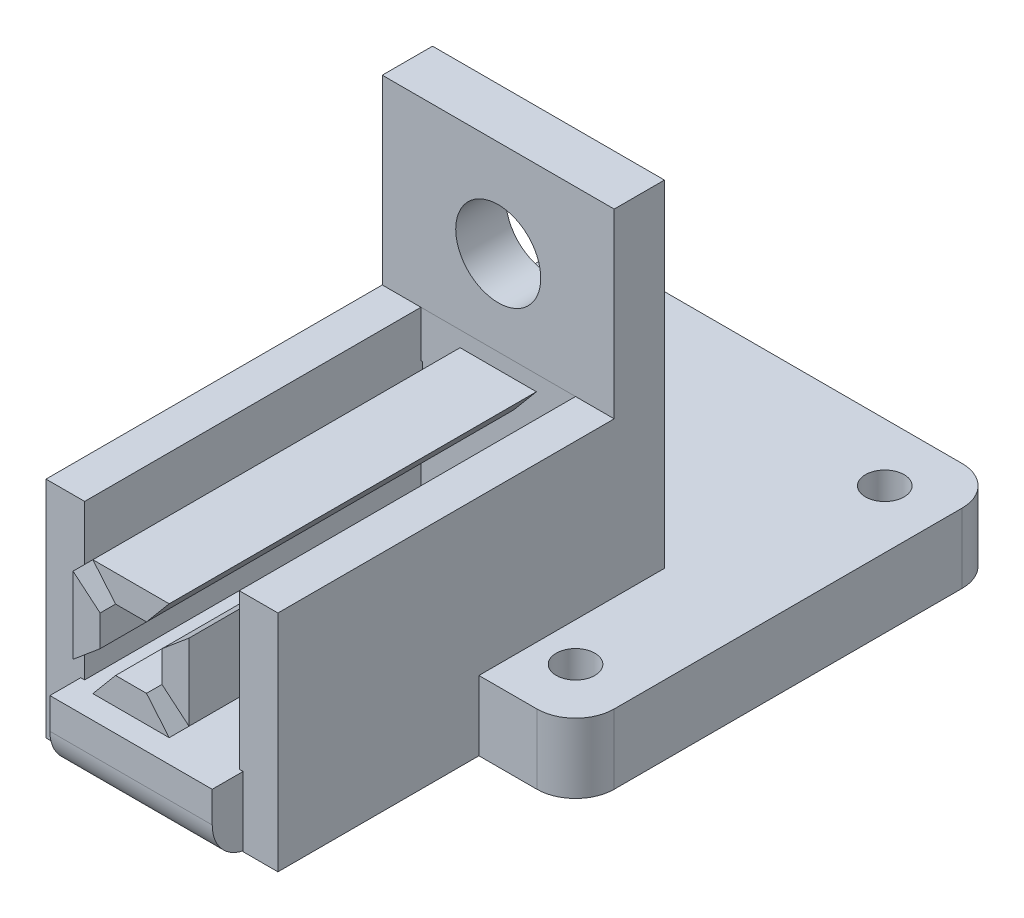
SolidWorks part; units mm, degrees
ref_plane "Front Plane" through (0, 0, 0) normal (0, 0, 1) x (1, 0, 0)
ref_plane "Top Plane" through (0, 0, 0) normal (0, 1, 0) x (1, 0, 0)
ref_plane "Right Plane" through (0, 0, 0) normal (1, 0, 0) x (0, 0, -1)
sketch "Sketch1" plane through (0, 0, 0) normal (0, 1, 0) x (1, 0, 0)
  line L0 (27.5, 55) -> (27.5, 0) construction
  line L1 (5, 0) -> (50, 0)
  line L2 (0, 5) -> (0, 50)
  line L3 (5, 55) -> (50, 55)
  line L4 (55, 5) -> (55, 50)
  line L5 (0, 55) -> (7.5, 55) construction
  line L6 (0, 55) -> (0, 47.5) construction
  line L7 (0, 47.5) -> (7.5, 47.5) construction
  line L8 (7.5, 55) -> (7.5, 47.5) construction
  line L9 (0, 27.5) -> (55, 27.5) construction
  circle A0 centre (7.5, 47.5) radius 2.5
  circle A1 centre (47.5, 47.5) radius 2.5
  circle A2 centre (47.5, 7.5) radius 2.5
  circle A3 centre (7.5, 7.5) radius 2.5
  arc A4 (50, 0) -> (55, 5) centre (50, 5) ccw
  arc A5 (50, 55) -> (55, 50) centre (50, 50) cw
  arc A6 (0, 50) -> (5, 55) centre (5, 50) cw
  arc A7 (5, 0) -> (0, 5) centre (5, 5) cw
  point P23 (55, 55)
  point P29 (0, 0)
  dimension "D3" = 2
  dimension "D5" = 5
  dimension "D1" = 55
  dimension "D2" = 55
  dimension "D4" = 2
extrude "Boss-Extrude2" add sketch "Sketch1" along normal blind 8 and the other way blind 1
sketch "Sketch2" plane through (0, 8, 0) normal (0, 1, 0) x (1, 0, 0)
  line L0 (0, 27.5) -> (55, 27.5)
  line L1 (0, 50) -> (0, 5) construction
  line L2 (55, 5) -> (55, 50) construction
  line L4 (0, 27.5) -> (55, 27.5)
  line L5 (0, 27.5) -> (0, 55)
  line L6 (0, 55) -> (55, 55)
  line L7 (55, 27.5) -> (55, 55)
  dimension "D1" = 27.5
sketch "Sketch5" plane through (0, 8, 0) normal (0, 1, 0) x (1, 0, 0)
  line L0 (27.5, 27.5) -> (27.5, 0)
  line L2 (5, 0) -> (50, 0) construction
  line L3 (27.5, 27.5) -> (27.5, 24)
  line L5 (27.5, 24) -> (23, 24)
  line L6 (27.5, 24) -> (27.5, 17.5)
  line L7 (27.5, 17.5) -> (23, 17.5)
  line L8 (23, 24) -> (23, 17.5)
  line L9 (27.5, 24) -> (32, 24)
  line L10 (27.5, 24) -> (27.5, 17.5)
  line L11 (27.5, 17.5) -> (32, 17.5)
  line L12 (32, 24) -> (32, 17.5)
  dimension "D1" = 3.5
  dimension "D2" = 6.5
  dimension "D3" = 4.5
  dimension "D4" = 4.5
  dimension "D5" = 6.5
extrude "Boss-Extrude3" add sketch "Sketch5" along normal blind 14.5 contours L5 L8 L7 L0 | L12 L9 L0 L11 region at (29.75, 8, -20.75) region at (25.25, 8, -20.75)
sketch "Sketch6" plane through (0, 0, -24) normal (0, 0, -1) x (-1, 0, 0)
  line L0 (-27.5, 8) -> (-27.5, 17)
  line L1 (-32, 8) -> (-23, 8) construction
  circle A0 centre (-27.5, 17) radius 4
  dimension "D2" = 8
  dimension "D1" = 9
extrude "Cut-Extrude4" cut sketch "Sketch6" against normal blind 1.5 contours A0 region at (24.7516, 14.2516, -24)
sketch "Sketch11" plane through (0, 0, -24) normal (0, 0, -1) x (-1, 0, 0)
  line L0 (-27.5, 22.5) -> (-25.5, 22.5)
  line L1 (-32.4368, 26) -> (-22.5632, 26)
  line L2 (-32, 22.5) -> (-23, 22.5) construction
  line L3 (-25.5, 22.5) -> (-27.5, 22.5)
  line L4 (-25.5, 22.5) -> (-29.5, 22.5)
  line L5 (-25.5, 22.5) -> (-25.5, 26)
  line L6 (-25.5, 26) -> (-29.5, 26)
  line L7 (-29.5, 22.5) -> (-29.5, 26)
  line L8 (-22.5632, 26) -> (-25.5, 22.5)
  line L9 (-29.5, 22.5) -> (-32.4368, 26)
  point P10 (-27.5, 26)
  line M9 (-23, 22.5) -> (-32, 22.5)
  dimension "D1" = 2
  dimension "D2" = 4
  dimension "D3" = 3.5
  dimension "D4" = 40
sketch "Sketch12" plane through (0, 8, 0) normal (0, 1, 0) x (1, 0, 0)
  line L0 (27.5, 17.5) -> (27.5, 0)
  line L1 (32, 17.5) -> (23, 17.5) construction
  line L2 (5, 0) -> (50, 0) construction
  line L3 (17, 0) -> (17, -30)
  line L4 (17, 0) -> (38, 0)
  line L5 (27.5, 0) -> (27.5, -30)
  line L6 (17, -30) -> (38, -30)
  line L7 (38, 0) -> (38, -30)
  point P9 (23.9675, 0)
  line M9 (5, 0) -> (50, 0)
  dimension "D1" = 30
  dimension "D2" = 10.5
extrude "Boss-Extrude7" add sketch "Sketch12" against normal blind 9 contours L7 L5 L6 M9 | L3 L6 L5 M9 region at (22.25, 8, 15) region at (32.75, 8, 15)
sketch "Sketch15" plane through (0, 22.5, 0) normal (0, 1, 0) x (1, 0, 0)
  line L0 (32, 24) -> (32, 17.5) construction
  line L1 (32, 17.5) -> (23, 17.5)
  line L2 (32, 17.5) -> (32, 24)
  line L3 (32, 24) -> (23, 24)
  line L4 (23, 17.5) -> (23, 24)
  line L5 (32, 17.5) -> (23, 17.5) construction
extrude "Boss-Extrude8" add sketch "Sketch15" along normal blind 3.5
extrude "Boss-Extrude9" add sketch "Sketch11" against normal blind 54 contours L9 L7 L1 | L7 L5 L1 M9 | L8 L1 L5 region at (27.5, 24.25, -24) region at (24.5211, 24.8333, -24) region at (30.4789, 24.8333, -24)
fillet "Fillet4" radius 5 1 edges at (27.5, -1, 30)
sketch "Sketch18" plane through (0, 26, 0) normal (0, 1, 0) x (1, 0, 0)
  line L0 (32.4368, -30) -> (32.4368, 24) construction
  line L1 (22.5632, 24) -> (32.4368, 24)
  line L2 (22.5632, 24) -> (22.5632, 17.5)
  line L3 (22.5632, 17.5) -> (32.4368, 17.5)
  line L4 (32.4368, 24) -> (32.4368, 17.5)
  dimension "D1" = 6.5
extrude "Boss-Extrude11" add sketch "Sketch18" along normal blind 0.5
sketch "Sketch20" plane through (0, 8, 0) normal (0, 1, 0) x (1, 0, 0)
  line L0 (27.5, -1030) -> (27.5, 48970) construction
  line L1 (17, -30) -> (38, -30) construction
  line L2 (32, 17.5) -> (23, 17.5) construction
  line L3 (27.5, 17.5) -> (16.5, 17.5)
  line L4 (27.5, 17.5) -> (27.5, 0)
  line L5 (27.5, 0) -> (16.5, 0)
  line L6 (16.5, 17.5) -> (16.5, 0)
  line L7 (27.5, 17.5) -> (16.5, 0) construction
  line L8 (27.5, 0) -> (16.5, 17.5) construction
  line L10 (27.5, 17.5) -> (38.5, 17.5)
  line L11 (27.5, 17.5) -> (27.5, 0)
  line L12 (27.5, 0) -> (38.5, 0)
  line L13 (38.5, 17.5) -> (38.5, 0)
  line L14 (27.5, 17.5) -> (38.5, 0) construction
  line L15 (27.5, 0) -> (38.5, 17.5) construction
  line L16 (38.5, 17.5) -> (42.5, 17.5)
  line L17 (38.5, 17.5) -> (38.5, 0)
  line L18 (38.5, 0) -> (42.5, 0)
  line L19 (42.5, 17.5) -> (42.5, 0)
  line L21 (16.5, 17.5) -> (12.5, 17.5)
  line L22 (16.5, 17.5) -> (16.5, 0)
  line L23 (16.5, 0) -> (12.5, 0)
  line L24 (12.5, 17.5) -> (12.5, 0)
  line L26 (42.5, 0) -> (38.5, 0)
  line L27 (42.5, 0) -> (42.5, 17.5)
  line L28 (42.5, 17.5) -> (38.5, 17.5)
  line L29 (38.5, 0) -> (38.5, 17.5)
  line L30 (16.5, 0) -> (12.5, 0)
  line L31 (16.5, 0) -> (16.5, 17.5)
  line L32 (16.5, 17.5) -> (12.5, 17.5)
  line L33 (12.5, 0) -> (12.5, 17.5)
  point P5 (27.5, -30)
  point P9 (22, 8.75)
  point P14 (33, 8.75)
  line M12 (5, 0) -> (17, 0)
  line M16 (38, 0) -> (50, 0)
  dimension "D2" = 11
  dimension "D3" = 17.5
  dimension "D4" = 4
extrude "Boss-Extrude12" add sketch "Sketch20" along normal blind 18 contours L21 L24 L6 M12 | L19 L16 L13 M16 region at (14.5, 8, -8.75) region at (40.5, 8, -8.75)
sketch "Sketch21" plane through (12.5, 0, 0) normal (-1, 0, 0) x (0, 0, 1)
  line L0 (-17.5, 26) -> (-17.5, 8) construction
  line L1 (0, 26) -> (-17.5, 26)
  line L2 (0, 26) -> (0, 24)
  line L3 (0, 24) -> (-17.5, 24)
  line L4 (-17.5, 26) -> (-17.5, 24)
  dimension "D1" = 2
sketch "Sketch22" plane through (12.5, 0, 0) normal (-1, 0, 0) x (0, 0, 1)
  line L1 (-17.5, 24) -> (0, 24)
  line L2 (-17.5, 24) -> (-17.5, 28)
  line L3 (-17.5, 28) -> (0, 28)
  line L4 (0, 24) -> (0, 28)
  dimension "D1" = 4
extrude "Boss-Extrude13" add sketch "Sketch22" along normal blind 11 and the other way blind 4 contours L3 L4 L1 L2
sketch "Sketch25" plane through (0, 28, 0) normal (0, 1, 0) x (1, 0, 0)
  line L2 (1.5, 17.5) -> (16.5, 17.5) construction
  line L3 (1.5, 0) -> (3.5, 0)
  line L4 (1.5, 0) -> (1.5, 17.5)
  line L5 (1.5, 17.5) -> (3.5, 17.5)
  line L6 (3.5, 0) -> (3.5, 17.5)
  dimension "D1" = 2
extrude "Boss-Extrude14" add sketch "Sketch25" along normal blind 41
sketch "Sketch28" plane through (1.5, 0, 0) normal (-1, 0, 0) x (0, 0, 1)
  line L2 (0, 69) -> (-41, 69)
  line L3 (0, 69) -> (0, 24)
  line L4 (0, 24) -> (-41, 24)
  line L5 (-41, 69) -> (-41, 24)
  dimension "D1" = 45
  dimension "D2" = 41
extrude "Boss-Extrude15" add sketch "Sketch28" against normal blind 2
sketch "Sketch29" plane through (1.5, 0, 0) normal (-1, 0, 0) x (0, 0, 1)
  line L1 (0, 24) -> (-5, 24)
  line L2 (0, 24) -> (0, 33)
  line L3 (0, 33) -> (-5, 33)
  line L4 (-5, 24) -> (-5, 33)
  circle A0 centre (-5, 33) radius 1.75
  circle A1 centre (-36, 33) radius 1.75
  circle A2 centre (-36, 64) radius 1.75
  circle A3 centre (-5, 64) radius 1.75
  dimension "D3" = 3.5
  dimension "D6" = 31
  dimension "D1" = 9
  dimension "D2" = 5
  dimension "D7" = 31
  dimension "D4" = 2
  dimension "D5" = 2
extrude "Cut-Extrude8" cut sketch "Sketch29" against normal blind 9 contours A1 | A3 | A0 | A2 region at (1.5, 33, -36) region at (1.5, 64, -5)
sketch "Sketch30" plane through (42.5, 0, 0) normal (1, 0, 0) x (0, 0, -1)
  line L0 (17.5, 26) -> (17.5, 8) construction
  line L1 (0, 26) -> (17.5, 26)
  line L2 (0, 26) -> (0, 24)
  line L3 (0, 24) -> (17.5, 24)
  line L4 (17.5, 26) -> (17.5, 24)
  line L6 (0, 24) -> (17.5, 24)
  line L7 (0, 24) -> (0, 28)
  line L8 (0, 28) -> (17.5, 28)
  line L9 (17.5, 24) -> (17.5, 28)
  line M4 (17.5, 8) -> (17.5, 26)
  line M5 (17.5, 26) -> (0, 26)
  line M6 (0, 26) -> (0, 8)
  dimension "D1" = 2
  dimension "D2" = 4
extrude "Boss-Extrude16" add sketch "Sketch30" along normal blind 9 and the other way blind 4 contours L3 M6 M4 M5 | L9 L8 L7 M5 region at (42.5, 27, -8.75) region at (42.5, 25, -8.75)
sketch "Sketch31" plane through (3.5, 0, 0) normal (1, 0, 0) x (0, 0, -1)
  line L1 (41, 69) -> (20.5, 69)
  line L2 (41, 69) -> (41, 47)
  line L3 (41, 47) -> (20.5, 47)
  line L4 (20.5, 69) -> (20.5, 47)
  circle A0 centre (20.5, 47) radius 10
  dimension "D3" = 20
  dimension "D1" = 22
  dimension "D2" = 20.5
extrude "Cut-Extrude9" cut sketch "Sketch31" against normal blind 9 contours L4 A0 L3 | L3 A0 L4 region at (3.5, 51.2441, -24.7441) region at (3.5, 45.5853, -19.0853)
sketch "Sketch32" plane through (0, 0, -17.5) normal (0, 0, -1) x (-1, 0, 0)
  line L1 (-16.5, 28) -> (-3.5, 28)
  line L2 (-16.5, 28) -> (-16.5, 24)
  line L3 (-16.5, 24) -> (-3.5, 24)
  line L4 (-3.5, 28) -> (-3.5, 24)
extrude "Boss-Extrude17" add sketch "Sketch32" along normal blind 23.5
sketch "Sketch33" plane through (0, 8, 0) normal (0, 1, 0) x (1, 0, 0)
  line L0 (38.5, 17.5) -> (38.5, 0)
  line L1 (38.5, 17.5) -> (38, 17.5)
  line L2 (38.5, 0) -> (38, 0)
  line L3 (38, 17.5) -> (38, 0)
  line L4 (16.5, 17.5) -> (16.5, 0)
  line L5 (16.5, 17.5) -> (17, 17.5)
  line L6 (16.5, 0) -> (17, 0)
  line L7 (17, 17.5) -> (17, 0)
  dimension "D1" = 0.5
  dimension "D2" = 0.5
extrude "Boss-Extrude18" add sketch "Sketch33" along normal blind 20
sketch "Sketch34" plane through (0, 0, 0) normal (0, 0, 1) x (1, 0, 0)
  line L0 (42.5, 24) -> (42.5, 8) construction
  line L1 (51.5, 28) -> (42.5, 28)
  line L2 (51.5, 28) -> (51.5, 24)
  line L3 (51.5, 24) -> (42.5, 24)
  line L4 (42.5, 28) -> (42.5, 24)
  line L5 (42.5, 24) -> (51.5, 24) construction
  line L7 (42.5, 28) -> (38, 28)
  line L8 (42.5, 28) -> (42.5, -1)
  line L9 (42.5, -1) -> (38, -1)
  line L10 (38, 28) -> (38, -1)
  line L11 (17, 28) -> (1.5, 28)
  line L12 (17, 28) -> (17, 24)
  line L13 (17, 24) -> (1.5, 24)
  line L14 (1.5, 28) -> (1.5, 24)
  line L15 (12.5, 24) -> (17, 24)
  line L16 (12.5, 24) -> (12.5, -1)
  line L17 (12.5, -1) -> (17, -1)
  line L18 (17, 24) -> (17, -1)
  line M1 (42.5, 8) -> (42.5, 24)
  line M2 (42.5, 24) -> (51.5, 24)
  line M3 (51.5, 24) -> (51.5, 28)
  line M4 (51.5, 28) -> (38, 28)
  line M5 (38, 28) -> (38, 8)
  line M6 (38, 8) -> (38, -1)
  line M7 (38, -1) -> (50, -1)
extrude "Boss-Extrude19" add sketch "Sketch34" along normal blind 26 contours L18 L13 L16 L17 | L11 L14 L13 L12 | L8 L4 M1 M4 M5 M6 M7 | L4 M4 M2 M3 region at (47, 26, 0) region at (40.25, 13.5, 0) region at (9.25, 26, 0) region at (14.75, 11.5, 0)
sketch "Sketch35" plane through (0, 0, -17.5) normal (0, 0, 1) x (1, 0, 0)
  line L1 (32.4368, 26.5) -> (22.5632, 26.5)
  line L2 (32.4368, 26.5) -> (32.4368, 26)
  line L3 (32.4368, 26) -> (22.5632, 26)
  line L4 (22.5632, 26.5) -> (22.5632, 26)
extrude "Boss-Extrude20" add sketch "Sketch35" along normal blind 47.5
sketch "Sketch37" plane through (0, 0, -17.5) normal (0, 0, 1) x (1, 0, 0)
  line L0 (27.5, 8) -> (29.5, 8)
  line L2 (32, 8) -> (23, 8) construction
  line L3 (29.5, 12) -> (33.1362, 7.6666)
  line L4 (29.5, 8) -> (25.5, 8)
  line L5 (29.5, 8) -> (29.5, 12)
  line L6 (29.5, 12) -> (25.5, 12)
  line L7 (25.5, 8) -> (25.5, 12)
  line L8 (25.5, 12) -> (21.8638, 7.6666)
  line L9 (21.8638, 7.6666) -> (33.1362, 7.6666)
  line M8 (32, 8) -> (32, 25.4794)
  line M12 (23, 25.4794) -> (23, 8)
  line M13 (23, 8) -> (32, 8)
  dimension "D1" = 2
  dimension "D2" = 4
  dimension "D3" = 4
  dimension "D4" = 40
  dimension "D5" = 40
extrude "Boss-Extrude21" add sketch "Sketch37" along normal blind 47.5 contours L7 L8 M12 M13 | L7 L5 L6 M13 | L5 L3 M13 M8 | L8 L9 L3 M8 M13 M12 region at (27.5, 10, -17.5) region at (27.5, 7.9298, -17.5) region at (30.5027, 9.4025, -17.5) region at (24.4973, 9.4025, -17.5)
sketch "Sketch38" plane through (0, 0, 30) normal (0, 0, 1) x (1, 0, 0)
  line L1 (22.5632, 26.5) -> (22.1436, 26.5)
  line L2 (22.5632, 26.5) -> (22.5632, 8)
  line L3 (22.5632, 8) -> (22.1436, 8)
  line L4 (22.1436, 26.5) -> (22.1436, 8)
  line L5 (32.4368, 26.5) -> (32.8564, 26.5)
  line L6 (32.4368, 26.5) -> (32.4368, 8)
  line L7 (32.4368, 8) -> (32.8564, 8)
  line L8 (32.8564, 26.5) -> (32.8564, 8)
extrude "Cut-Extrude10" cut sketch "Sketch38" against normal blind 90.5
sketch "Sketch39" plane through (0, 0, 30) normal (0, 0, 1) x (1, 0, 0)
  line L0 (27.784, 26.1035) -> (27.5, 26.5)
  line L1 (32.4368, 26.5) -> (38, 26.5)
  line L2 (32.4368, 26.5) -> (32.4368, 8)
  line L3 (32.4368, 8) -> (38, 8)
  line L4 (38, 26.5) -> (38, 8)
  line L5 (32.4368, 26.5) -> (22.5632, 26.5) construction
  line L6 (27.5, 26.5) -> (27.5, 8)
  line L7 (38, 17.25) -> (38, 19.25)
  line L8 (34, 19.25) -> (38, 22.6064)
  line L9 (38, 19.25) -> (34, 19.25)
  line L10 (38, 19.25) -> (38, 15.25)
  line L11 (38, 15.25) -> (34, 15.25)
  line L12 (34, 19.25) -> (34, 15.25)
  line L13 (34, 15.25) -> (38, 11.8936)
  line L14 (22.5632, 8.5) -> (21.9673, 8)
  line L15 (17, 8) -> (22.5632, 8) construction
  line L16 (17, 22.6064) -> (17.7151, 22.6064)
  line L17 (38, 22.6064) -> (37.2849, 22.6064)
  line L18 (38, 22.6064) -> (38, 22.0064)
  line L19 (38, 22.0064) -> (37.2849, 22.0064)
  line L20 (37.2849, 22.6064) -> (37.2849, 22.0064)
  line L21 (38, 11.8936) -> (37.2849, 11.8936)
  line L22 (38, 11.8936) -> (38, 12.4936)
  line L23 (38, 12.4936) -> (37.2849, 12.4936)
  line L24 (37.2849, 11.8936) -> (37.2849, 12.4936)
  line L25 (17.7151, 22.6064) -> (17.7151, 22.0064)
  line L26 (17, 22.0064) -> (17.7151, 22.0064)
  line L27 (21, 19.25) -> (17, 22.6064)
  line L28 (21, 19.25) -> (21, 15.25)
  line L29 (17, 19.25) -> (21, 19.25)
  line L30 (17.7151, 11.8936) -> (17.7151, 12.4936)
  line L31 (17, 11.8936) -> (17.7151, 11.8936)
  line L32 (17, 12.4936) -> (17.7151, 12.4936)
  line L33 (17, 26.5) -> (17, 8)
  line L34 (17, 15.25) -> (21, 15.25)
  line L35 (21, 15.25) -> (17, 11.8936)
  line L36 (17, 19.25) -> (17, 22.0064)
  line L37 (17, 22.0064) -> (17.7151, 22.0064)
  line L38 (17.7151, 22.0064) -> (21, 19.25)
  line L39 (17, 19.25) -> (21, 19.25)
  dimension "D1" = 2
  dimension "D2" = 4
  dimension "D3" = 4
  dimension "D4" = 40
  dimension "D5" = 40
  dimension "D6" = 0.6
  dimension "D7" = 0.6
extrude "Boss-Extrude23" add sketch "Sketch39" against normal blind 47.5 contours L26 L33 L29 L27 | L33 L34 L28 L29 | L35 L34 L33 L32 | L23 L4 L11 L13 | L9 L12 L11 L4 | L4 L19 L8 L9 region at (36.6305, 20.3081, 30) region at (36, 17.25, 30) region at (36.6305, 14.1919, 30) region at (18.3695, 20.3081, 30) region at (19, 17.25, 30) region at (18.3695, 14.1919, 30)
ref_plane "Plane1" through (5, 8, 0) normal (0, 1, 0) x (1, 0, 0)
sketch "Sketch48" plane through (0, 8, 0) normal (0, 1, 0) x (1, 0, 0)
  line L1 (7.5, 24) -> (47.5, 24)
  line L3 (7.5, 17.5) -> (47.5, 17.5)
  line L7 (7.5, 17.5) -> (7.5, 24)
  line L15 (47.5, 24) -> (47.5, 17.5)
  line M3 (12.5, 17.5) -> (17, 17.5)
  line M8 (22.5632, 17.5) -> (23, 17.5)
  line M9 (23, 17.5) -> (23, 24)
  line M11 (32, 24) -> (32, 17.5)
  line M12 (32, 17.5) -> (32.4368, 17.5)
  line M17 (38, 17.5) -> (42.5, 17.5)
sketch "Sketch49" plane through (0, 0, -24) normal (0, 0, -1) x (-1, 0, 0)
  line L0 (-17.5, 3.5) -> (-27.5, 17)
  line L1 (-27.5, 17) -> (-17.5, 17)
  line L2 (-17.5, 17) -> (-17.5, 3.5)
  line L3 (-27.5, 17) -> (-37.5, 3.5)
  line L4 (-37.5, 3.5) -> (-37.5, 17)
  line L5 (-37.5, 17) -> (-27.5, 17)
  circle A0 centre (-37.5, 17) radius 4
  circle A1 centre (-17.5, 17) radius 4
  dimension "D1" = 8
  dimension "D2" = 8
extrude "Boss-Extrude31" add sketch "Sketch48" along normal blind 18.5 contours M12 M17 M11 | L15 | M8 M9 M3 | L7 region at (15.25, 8, -20.75) region at (39.75, 8, -20.75)
sketch "Sketch51" plane through (0, 0, -24) normal (0, 0, -1) x (-1, 0, 0)
  line L1 (-32.4593, 12.5515) -> (-22.8331, 12.5515)
  line L2 (-32.4593, 12.5515) -> (-32.4593, 21.6767)
  line L3 (-32.4593, 21.6767) -> (-22.8331, 21.6767)
  line L4 (-22.8331, 12.5515) -> (-22.8331, 21.6767)
extrude "Boss-Extrude32" add sketch "Sketch51" against normal blind 1.5
sketch "Sketch53" plane through (0, 0, -24) normal (0, 0, -1) x (-1, 0, 0)
  line L0 (-27.5, 17) -> (-27.5, 8)
  line L1 (-47.5, 8) -> (-7.5, 8) construction
  line L2 (-27.5, 8) -> (-27.5, 26.5)
  line L3 (-47.5, 26.5) -> (-16.5, 26.5) construction
  line L4 (-27.5, 17.25) -> (-23.5, 17.25)
  line L5 (-23.5, 17.25) -> (-31.5, 17.25)
  line L7 (-31.5, 13.25) -> (-23.5, 13.25)
  line L8 (-31.5, 13.25) -> (-31.5, 21.25)
  line L9 (-31.5, 21.25) -> (-23.5, 21.25)
  line L10 (-23.5, 13.25) -> (-23.5, 21.25)
  line L11 (-31.5, 13.25) -> (-23.5, 21.25) construction
  line L12 (-31.5, 21.25) -> (-23.5, 13.25) construction
  dimension "D1" = 4
  dimension "D2" = 4
  dimension "D3" = 8
  dimension "D4" = 8
sketch "Sketch54" plane through (0, 0, -17.5) normal (0, 0, 1) x (1, 0, 0)
  line L0 (27.5, 22.5) -> (27.5, 14.5)
  line L1 (29.5, 22.5) -> (25.5, 22.5) construction
  line L3 (23.5, 22.5) -> (31.5, 22.5)
  line L4 (23.5, 22.5) -> (23.5, 14.5)
  line L5 (23.5, 14.5) -> (31.5, 14.5)
  line L6 (31.5, 22.5) -> (31.5, 14.5)
  line L7 (23.5, 22.5) -> (31.5, 14.5) construction
  line L8 (23.5, 14.5) -> (31.5, 22.5) construction
  point P4 (27.5, 18.5)
  line M17 (29.5, 22.5) -> (25.5, 22.5)
  dimension "D1" = 8
  dimension "D2" = 8
  dimension "D3" = 8
extrude "Boss-Extrude35" add sketch "Sketch54" along normal blind 47.5 contours L6 L3 L0 L5 M17 | L4 L5 L0 L3 M17 region at (29.5, 18.5, -17.5) region at (25.5, 18.5, -17.5)
sketch "Sketch55" plane through (0, 0, 30) normal (0, 0, 1) x (1, 0, 0)
  line L1 (32.4368, 26.5) -> (22.5632, 26.5)
  line L2 (32.4368, 26.5) -> (32.4368, 26)
  line L3 (32.4368, 26) -> (22.5632, 26)
  line L4 (22.5632, 26.5) -> (22.5632, 26)
extrude "Cut-Extrude12" cut sketch "Sketch55" against normal blind 47.5
sketch "Sketch56" plane through (0, 0, 26) normal (0, 0, 1) x (1, 0, 0)
  line L1 (38, 28) -> (37.5, 28)
  line L2 (38, 28) -> (38, 8)
  line L3 (38, 8) -> (37.5, 8)
  line L4 (37.5, 28) -> (37.5, 8)
  line L5 (17, 28) -> (17.5, 28)
  line L6 (17, 28) -> (17, 8)
  line L7 (17, 8) -> (17.5, 8)
  line L8 (17.5, 28) -> (17.5, 8)
  dimension "D1" = 0.5
  dimension "D2" = 0.5
extrude "Boss-Extrude36" add sketch "Sketch56" against normal blind 43.5
sketch "Sketch57" plane through (0, 0, 30) normal (0, 0, 1) x (1, 0, 0)
  line L0 (31.5, 20.5) -> (31.5, 16.5)
  line L1 (35, 18.4644) -> (35, 13.5632)
  line L2 (25.5, 22.5) -> (29.5, 22.5)
  line L3 (29.5, 22.5) -> (32.4368, 26)
  line L4 (29.5, 22.5) -> (29.5, 26)
  line L5 (22.5632, 26) -> (32.4368, 26) construction
  line L6 (31.5, 22.5) -> (31.5, 14.5) construction
  line L7 (35, 13.5632) -> (31.5, 16.5)
  line L8 (31.5, 16.5) -> (35, 16.5)
  line L9 (31.5, 16.5) -> (31.5, 20.4288)
  line L10 (31.5, 20.4288) -> (35, 20.4288)
  line L11 (35, 16.5) -> (35, 20.4288)
  line L12 (35, 18.5356) -> (35, 23.4368)
  line L13 (35, 16.5) -> (31.5, 16.5)
  line L14 (35, 16.5) -> (35, 18.5)
  line L15 (35, 18.5) -> (31.5, 18.5)
  line L16 (31.5, 16.5) -> (31.5, 18.5)
  line L17 (35, 23.4368) -> (31.5, 20.5)
  line L18 (27.5, 22.5) -> (27.5, 14.5) construction
  line L19 (23.5, 14.5) -> (31.5, 14.5) construction
  line L20 (20, 13.5632) -> (23.5, 16.5)
  line L21 (23.5, 16.5) -> (20, 16.5)
  line L22 (20, 18.4644) -> (20, 13.5632)
  line L23 (20, 18.5356) -> (20, 23.4368)
  line L24 (20, 23.4368) -> (23.5, 20.5)
  line L25 (23.5, 20.5) -> (23.5, 16.5)
  line L26 (27.5, 18.5) -> (31.5, 18.5) construction
  line L27 (31.5, 18.5) -> (23.5, 18.5) construction
  line L28 (23.5, 20.5) -> (23.5, 16.5)
  line L29 (32.4368, 26) -> (22.5632, 26)
  line L30 (22.5632, 26) -> (25.5, 22.5)
  line L31 (25.5, 14.5) -> (29.5, 14.5)
  line L32 (22.5632, 11) -> (25.5, 14.5)
  line L33 (32.4368, 11) -> (22.5632, 11)
  line L34 (29.5, 14.5) -> (32.4368, 11)
  line L35 (23.5, 16.5) -> (20, 13.5632)
  line L36 (20, 13.5632) -> (20, 23.4368)
  line L37 (20, 23.4368) -> (23.5, 20.5)
  line L38 (23.5, 18.5) -> (23.5, 20.5)
  line M12 (23.5, 22.5) -> (23.5, 14.5)
  line M13 (23.5, 14.5) -> (31.5, 14.5)
  line M14 (31.5, 14.5) -> (31.5, 22.5)
  dimension "D1" = 2
  dimension "D2" = 3.5
  dimension "D3" = 130
extrude "Boss-Extrude37" add sketch "Sketch57" against normal blind 47.5 contours L12 L17 L0 L10 | L15 L11 L10 L9 | L11 L15 L8 L1 M14 | L8 L7 L1 | L34 L32 L33 M13 | L36 L22 L21 L28 L24 L23 M12 | L21 L22 L20 region at (33.8064, 21.432, 30) region at (21.1667, 15.5211, 30) region at (21.5934, 19.2999, 30) region at (27.5, 12.503, 30) region at (33.25, 19.4644, 30) region at (33.25, 17.5, 30) region at (33.8333, 15.5211, 30)
sketch "Sketch58" plane through (0, 0, 30) normal (0, 0, 1) x (1, 0, 0)
  line L1 (38, 22.0064) -> (37.2849, 22.0064)
  line L2 (38, 22.0064) -> (38, 12.4936)
  line L3 (38, 12.4936) -> (37.2849, 12.4936)
  line L4 (37.2849, 22.0064) -> (37.2849, 12.4936)
  line L5 (17, 22.0064) -> (17.7151, 22.0064)
  line L6 (17, 22.0064) -> (17, 12.4936)
  line L7 (17, 12.4936) -> (17.7151, 12.4936)
  line L8 (17.7151, 22.0064) -> (17.7151, 12.4936)
extrude "Cut-Extrude13" cut sketch "Sketch58" against normal blind 4
sketch "Sketch59" plane through (0, 0, 30) normal (0, 0, 1) x (1, 0, 0)
  line L0 (37.2849, 22.0064) -> (35, 20.0891)
  line L1 (35, 20.0891) -> (35, 14.4109)
  line L2 (35, 14.4109) -> (37.2849, 12.4936)
  line L3 (37.2849, 12.4936) -> (37.2849, 22.0064)
  line L4 (17.7151, 22.0064) -> (20, 20.0891)
  line L5 (20, 20.0891) -> (20, 14.4109)
  line L6 (20, 14.4109) -> (17.7151, 12.4936)
  line L7 (20, 14.4109) -> (17.7151, 12.4936) construction
  line L8 (17.7151, 12.4936) -> (17.7151, 22.0064)
extrude "Cut-Extrude15" cut sketch "Sketch59" against normal blind 47.5
sketch "Sketch60" plane through (0, 0, 26) normal (0, 0, 1) x (1, 0, 0)
  line L0 (17.7151, 12.4936) -> (17.7151, 22.0064) construction
  line L1 (37.2849, 22.0064) -> (37.5, 22.0064)
  line L2 (37.2849, 22.0064) -> (37.2849, 12.4936)
  line L3 (37.2849, 12.4936) -> (37.5, 12.4936)
  line L4 (37.5, 22.0064) -> (37.5, 12.4936)
  line L5 (17.5, 22.0064) -> (17.7151, 22.0064)
  line L6 (17.5, 22.0064) -> (17.5, 12.4936)
  line L7 (17.5, 12.4936) -> (17.7151, 12.4936)
  line L8 (17.7151, 22.0064) -> (17.7151, 12.4936)
extrude "Cut-Extrude16" cut sketch "Sketch60" against normal blind 47.5
sketch "Sketch61" plane through (0, 0, 30) normal (0, 0, 1) x (1, 0, 0)
  line L0 (32.4368, 8) -> (22.5632, 8)
  line L1 (22.5632, 8) -> (22.5632, 8.5)
  line L2 (22.5632, 8.5) -> (24.6609, 11)
  line L3 (24.6609, 11) -> (30.3391, 11)
  line L4 (30.3391, 11) -> (32.4368, 8.5)
  line L5 (32.4368, 8.5) -> (32.4368, 8)
extrude "Cut-Extrude17" cut sketch "Sketch61" against normal blind 47.5
sketch "Sketch62" plane through (0, 0, 30) normal (0, 0, 1) x (1, 0, 0)
  line L1 (23.5, 22.5) -> (31.5, 22.5)
  line L2 (23.5, 22.5) -> (23.5, 14.5)
  line L3 (23.5, 14.5) -> (31.5, 14.5)
  line L4 (31.5, 22.5) -> (31.5, 14.5)
extrude "Cut-Extrude18" cut sketch "Sketch62" against normal blind 47.5
sketch "Sketch63" plane through (0, 0, -41) normal (0, 0, -1) x (-1, 0, 0)
  line L1 (-3.5, 28) -> (-16.5, 28)
  line L2 (-3.5, 28) -> (-3.5, 24)
  line L3 (-3.5, 24) -> (-16.5, 24)
  line L4 (-16.5, 28) -> (-16.5, 24)
extrude "Cut-Extrude20" cut sketch "Sketch63" against normal blind 17
sketch "Sketch64" plane through (0, 0, -17.5) normal (0, 0, -1) x (-1, 0, 0)
  line L1 (-17.5, 26.5) -> (-16.5, 26.5)
  line L2 (-17.5, 26.5) -> (-17.5, 28)
  line L3 (-17.5, 28) -> (-16.5, 28)
  line L4 (-16.5, 26.5) -> (-16.5, 28)
extrude "Boss-Extrude38" add sketch "Sketch64" along normal blind 6.5
sketch "Sketch68" plane through (0, 0, -41) normal (0, 0, -1) x (-1, 0, 0)
  line L1 (-1.5, 69) -> (-3.5, 69)
  line L2 (-1.5, 69) -> (-1.5, 24)
  line L3 (-1.5, 24) -> (-3.5, 24)
  line L4 (-3.5, 69) -> (-3.5, 24)
extrude "Cut-Extrude23" cut sketch "Sketch68" against normal blind 17
sketch "Sketch69" plane through (0, 0, -24) normal (0, 0, -1) x (-1, 0, 0)
  line L1 (-3.5, 28) -> (-1.5, 28)
  line L2 (-3.5, 28) -> (-3.5, 69)
  line L3 (-3.5, 69) -> (-1.5, 69)
  line L4 (-1.5, 28) -> (-1.5, 69)
extrude "Cut-Extrude24" cut sketch "Sketch69" against normal blind 37
sketch "Sketch70" plane through (0, 0, -24) normal (0, 0, -1) x (-1, 0, 0)
  line L1 (-17.5, 26.5) -> (-1.5, 26.5)
  line L2 (-17.5, 26.5) -> (-17.5, 28)
  line L3 (-17.5, 28) -> (-1.5, 28)
  line L4 (-1.5, 26.5) -> (-1.5, 28)
  line L5 (-7.5, 24) -> (-1.5, 24)
  line L6 (-7.5, 24) -> (-7.5, 26.5)
  line L7 (-7.5, 26.5) -> (-1.5, 26.5)
  line L8 (-1.5, 24) -> (-1.5, 26.5)
  line M3 (-1.5, 24) -> (-1.5, 28)
  line M10 (-7.5, 24) -> (-1.5, 24)
extrude "Cut-Extrude25" cut sketch "Sketch70" against normal blind 6.5 contours L6 L1 M10 M3 | L1 L2 L3 L4 region at (4.5, 25.25, -24)
sketch "Sketch72" plane through (1.5, 0, 0) normal (-1, 0, 0) x (0, 0, 1)
  line L1 (-17.5, 28) -> (26, 28)
  line L2 (-17.5, 28) -> (-17.5, 24)
  line L3 (-17.5, 24) -> (26, 24)
  line L4 (26, 28) -> (26, 24)
extrude "Cut-Extrude26" cut sketch "Sketch72" against normal blind 11
sketch "Sketch73" plane through (51.5, 0, 0) normal (1, 0, 0) x (0, 0, -1)
  line L1 (17.5, 28) -> (-26, 28)
  line L2 (17.5, 28) -> (17.5, 24)
  line L3 (17.5, 24) -> (-26, 24)
  line L4 (-26, 28) -> (-26, 24)
extrude "Cut-Extrude27" cut sketch "Sketch73" against normal blind 9
sketch "Sketch74" plane through (7.5, 0, 0) normal (-1, 0, 0) x (0, 0, 1)
  line L1 (-24, 26.5) -> (-17.5, 26.5)
  line L2 (-24, 26.5) -> (-24, 8)
  line L3 (-24, 8) -> (-17.5, 8)
  line L4 (-17.5, 26.5) -> (-17.5, 8)
extrude "Cut-Extrude28" cut sketch "Sketch74" against normal blind 5
sketch "Sketch75" plane through (47.5, 0, 0) normal (1, 0, 0) x (0, 0, -1)
  line L1 (24, 26.5) -> (17.5, 26.5)
  line L2 (24, 26.5) -> (24, 8)
  line L3 (24, 8) -> (17.5, 8)
  line L4 (17.5, 26.5) -> (17.5, 8)
extrude "Cut-Extrude30" cut sketch "Sketch75" against normal blind 5
sketch "Sketch76" plane through (0, 26.5, 0) normal (0, 1, 0) x (1, 0, 0)
  line L1 (12.5, 24) -> (42.5, 24)
  line L2 (12.5, 24) -> (12.5, 17.5)
  line L3 (12.5, 17.5) -> (42.5, 17.5)
  line L4 (42.5, 24) -> (42.5, 17.5)
extrude "Boss-Extrude39" add sketch "Sketch76" along normal blind 1.5
sketch "Sketch81" plane through (0, 28, 0) normal (0, 1, 0) x (1, 0, 0)
  line L0 (42.5, 24) -> (42.5, -26) construction
  line L1 (12.5, 24) -> (42.5, 24)
  line L2 (12.5, 24) -> (12.5, 17.4984)
  line L3 (12.5, 17.4984) -> (42.5, 17.4984)
  line L4 (42.5, 24) -> (42.5, 17.4984)
extrude "Boss-Extrude44" add sketch "Sketch81" along normal blind 23.5
sketch "Sketch82" plane through (0, 0, -24) normal (0, 0, -1) x (-1, 0, 0)
  line L0 (-20, 46.5) -> (-35, 31.5) construction
  line L1 (-35, 46.5) -> (-20, 46.5)
  line L2 (-35, 46.5) -> (-35, 31.5)
  line L3 (-35, 31.5) -> (-20, 31.5)
  line L4 (-20, 46.5) -> (-20, 31.5)
  line L5 (-42.5, 51.5) -> (-12.5, 51.5) construction
  line L6 (-20, 39) -> (-12.5, 39) construction
  line L7 (-12.5, 51.5) -> (-12.5, 8) construction
  line L8 (-35, 39) -> (-42.5, 39) construction
  line L9 (-42.5, 8) -> (-42.5, 51.5) construction
  line L10 (-20, 31.5) -> (-35, 46.5) construction
  circle A0 centre (-33.5, 45) radius 1.5
  circle A1 centre (-21.5, 45) radius 1.5
  circle A2 centre (-21.5, 33) radius 1.5
  circle A3 centre (-33.5, 33) radius 1.5
  circle A4 centre (-27.5, 39) radius 5.5
  point P16 (-27.5, 39)
  point P26 (-27.5, 39)
  dimension "D4" = 4
  dimension "D5" = 11
  dimension "D6" = 3
  dimension "D1" = 5
  dimension "D2" = 15
  dimension "D3" = 15
extrude "Cut-Extrude31" cut sketch "Sketch82" against normal blind 5 contours A0 | A2 | A1 | A3
extrude "Cut-Extrude32" cut sketch "Sketch82<4>" against normal up to next contours A4
sketch "Sketch82<4>" plane through (0, 0, -24) normal (0, 0, -1) x (-1, 0, 0) same geometry as "Sketch82"
